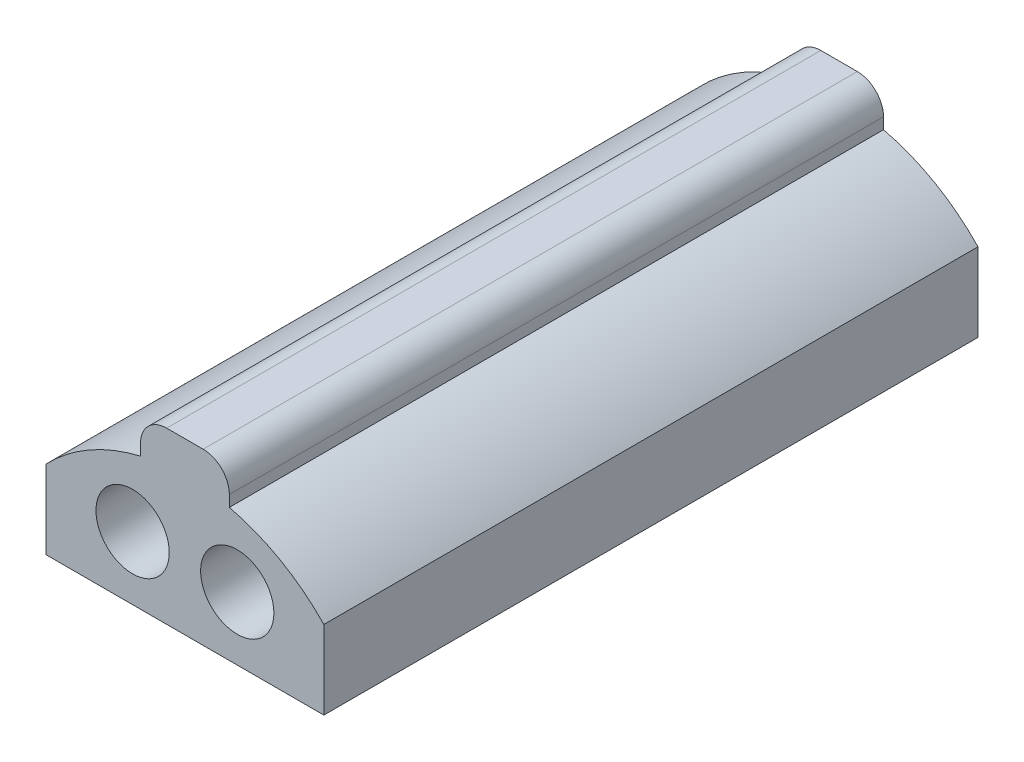
SolidWorks part; units mm, degrees
material "Thornel Mat VMA"
ref_plane "Front Plane" through (0, 0, 0) normal (0, 0, 1) x (1, 0, 0)
ref_plane "Top Plane" through (0, 0, 0) normal (0, 1, 0) x (1, 0, 0)
ref_plane "Right Plane" through (0, 0, 0) normal (1, 0, 0) x (0, 0, -1)
sketch "Sketch1" plane through (0, 0, 0) normal (0, 0, 1) x (1, 0, 0)
  line L0 (-10.6184, 0) -> (10.6184, 0)
  line L1 (10.6184, 0) -> (10.6184, 6)
  line L2 (3.3956, 10.1368) -> (3.3956, 10.9893)
  line L3 (1.3956, 12.9893) -> (-1.3956, 12.9893)
  line L4 (-3.3956, 10.9893) -> (-3.3956, 10.1368)
  line L5 (-10.6184, 6) -> (-10.6184, 0)
  arc A0 (10.6184, 6) -> (3.3956, 10.1368) centre (0, -4.1656) ccw construction
  arc A3 (-3.3956, 10.1368) -> (-10.6184, 6) centre (0, -4.1656) ccw construction
  arc A4 (10.6184, 6) -> (3.3956, 10.1368) centre (0, -4.1656) ccw
  arc A5 (-3.3956, 10.1368) -> (-10.6184, 6) centre (0, -4.1656) ccw
  arc A6 (1.3956, 12.9893) -> (3.3956, 10.9893) centre (1.3956, 10.9893) cw
  arc A7 (-1.3956, 12.9893) -> (-3.3956, 10.9893) centre (-1.3956, 10.9893) ccw
  point P14 (0, 0)
  dimension "D2" = 29.4
  dimension "D5" = 10.1368
  dimension "D6" = 2
  dimension "D1" = 21.2368
  dimension "D3" = 4.1656
  dimension "D4" = 12.9893
extrude "Boss-Extrude1" add sketch "Sketch1" against normal blind 50
sketch "Sketch2" plane through (0, 0, 0) normal (0, 0, 1) x (1, 0, 0)
  line L0 (-10.6184, 0) -> (10.6184, 0) construction
  circle A0 centre (-4, 4.84) radius 2.8
  circle A1 centre (4, 4.84) radius 2.8
  dimension "D3" = 5.6
  dimension "D1" = 4
  dimension "D2" = 4
  dimension "D4" = 4.84
extrude "Cut-Extrude1" cut sketch "Sketch2" against normal through all
equation "\"D2@Sketch2\"=\"D1@Sketch2\""
